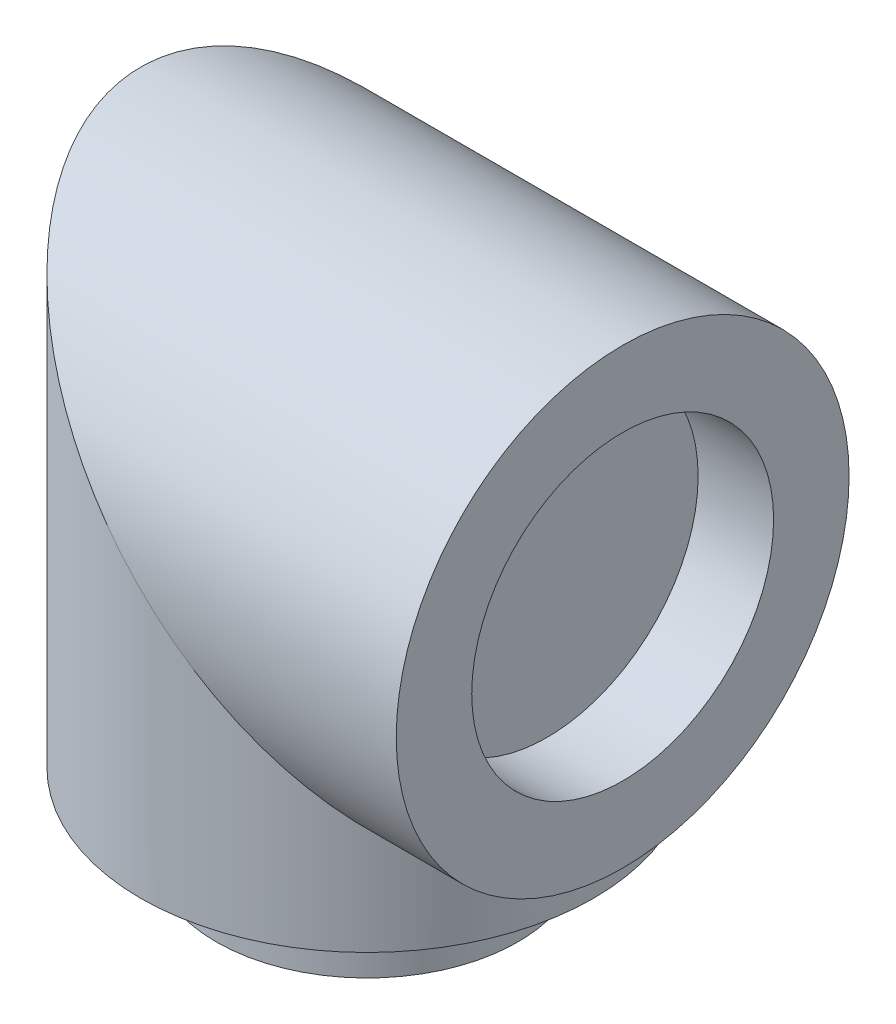
SolidWorks part; units mm, degrees
material "Polybutadiene (PB)"
ref_plane "Front Plane" through (0, 0, 0) normal (0, 0, 1) x (1, 0, 0)
ref_plane "Top Plane" through (0, 0, 0) normal (0, 1, 0) x (1, 0, 0)
ref_plane "Right Plane" through (0, 0, 0) normal (1, 0, 0) x (0, 0, -1)
sketch "Sketch1" plane through (0, 0, 0) normal (0, 1, 0) x (1, 0, 0)
  circle A0 centre (0, 0) radius 50.8
  dimension "D1" = 101.6
extrude "Boss-Extrude1" add sketch "Sketch1" along normal blind 25.4
sketch "Sketch2" plane through (0, 25.4, 0) normal (0, 1, 0) x (1, 0, 0)
  circle A0 centre (0, 0) radius 76.2
  dimension "D1" = 152.4
sketch "Sketch3" plane through (0, 0, 0) normal (0, 0, 1) x (1, 0, 0)
  line L0 (0, 25.4) -> (0, 50.8)
  line L1 (76.2, 25.4) -> (-76.2, 25.4) construction
  line L2 (50.8, 101.6) -> (127, 101.6)
  arc A0 (0, 50.8) -> (50.8, 101.6) centre (50.8, 50.8) cw
  point P8 (0, 101.6)
  dimension "D3" = 50.8
  dimension "D1" = 76.2
  dimension "D2" = 127
extrude "Boss-Extrude2" add sketch "Sketch2" along normal blind 89.9 contours A0
sketch "Sketch4" plane through (0, 0, 0) normal (1, 0, 0) x (0, 0, -1)
  line L0 (76.2, 115.3) -> (-76.2, 115.3) construction
  circle A0 centre (0, 115.3) radius 76.2
extrude "Boss-Extrude3" add sketch "Sketch4" along normal mid plane 172
sketch "Sketch5" plane through (0, 25.4, 0) normal (0, -1, 0) x (1, 0, 0)
  line L0 (0, 148.4733) -> (0, -148.4733)
  arc A0 (0, 148.4733) -> (0, -148.4733) centre (0, 0) ccw
  circle A1 centre (0, 0) radius 76.2
  arc A2 (0, 76.2) -> (0, -76.2) centre (0, 0) ccw
  circle M3 centre (0, 0) radius 76.2
  dimension "D1" = 0
extrude "Cut-Extrude1" cut sketch "Sketch5" against normal through all contours L0 A0 M3 region at (-3.32, 25.4, 112.3367)
sketch "Sketch6" plane through (86, 0, 0) normal (1, 0, 0) x (0, 0, -1)
  circle A1 centre (0, 115.3) radius 76.2
  circle A2 centre (0, 115.3) radius 76.2
  dimension "D1" = 0
sketch "Sketch7" plane through (86, 0, 0) normal (1, 0, 0) x (0, 0, -1)
  circle A0 centre (0, 115.3) radius 50.8
  dimension "D1" = 101.6
extrude "Cut-Extrude2" cut sketch "Sketch7" against normal blind 25.4
equation "\"`\"=0.1"
